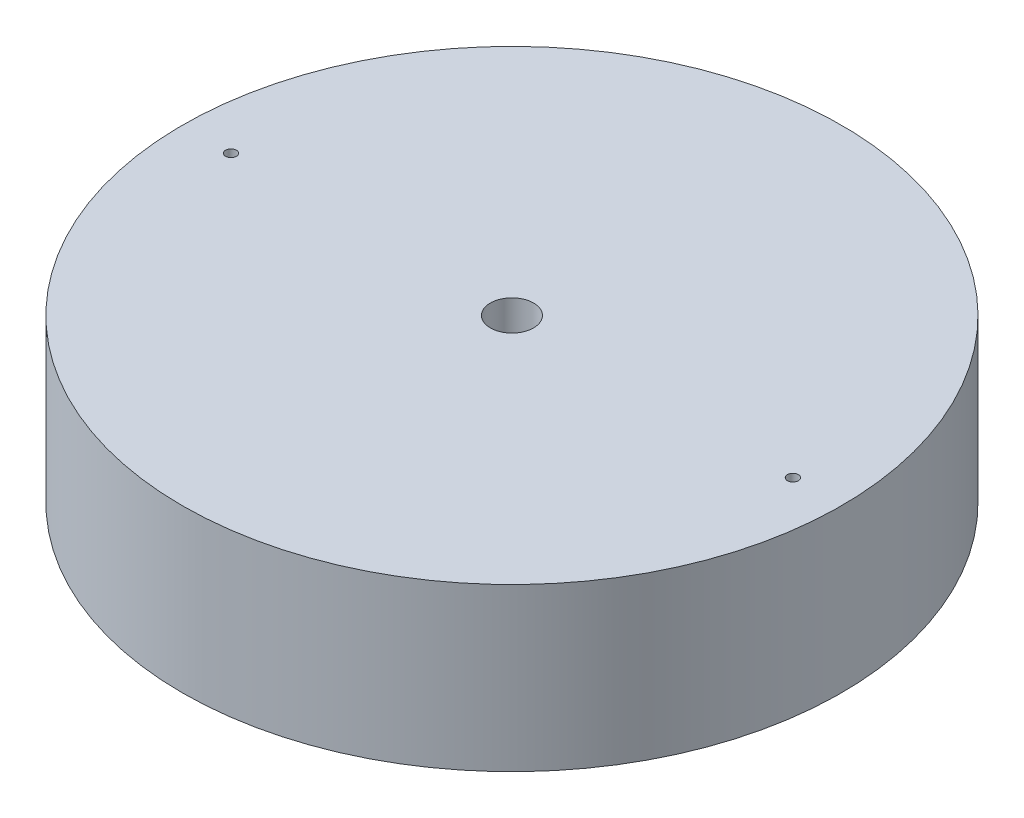
SolidWorks part; units mm, degrees
material "7075-T6 (SN)"
ref_plane "Front Plane" through (0, 0, 0) normal (0, 0, 1) x (1, 0, 0)
ref_plane "Top Plane" through (0, 0, 0) normal (0, 1, 0) x (1, 0, 0)
ref_plane "Right Plane" through (0, 0, 0) normal (1, 0, 0) x (0, 0, -1)
sketch "Sketch1" plane through (0, 0, 0) normal (0, 1, 0) x (1, 0, 0)
  circle A0 centre (0, 0) radius 32.5
extrude "Boss-Extrude1" add sketch "Sketch1" along normal blind 15
sketch "Sketch2" plane through (0, 15, 0) normal (0, 1, 0) x (1, 0, 0)
  circle A0 centre (0, 0) radius 30.5
  circle A1 centre (0, 0) radius 32.5
extrude "Cut-Extrude2" cut sketch "Sketch2" against normal blind 30
sketch "Sketch3" plane through (0, 0, 0) normal (0, -1, 0) x (1, 0, 0)
  circle A0 centre (0, 0) radius 24
  circle A1 centre (0, 0) radius 28
  dimension "D1" = 4
extrude "Cut-Extrude3" cut sketch "Sketch3" against normal blind 7
sketch "Sketch5" plane through (0, 15, 0) normal (0, 1, 0) x (1, 0, 0)
  circle A0 centre (0, 0) radius 26 construction
  circle A1 centre (-26, 0) radius 0.5
  circle A2 centre (26, 0) radius 0.5
extrude "Cut-Extrude5" cut sketch "Sketch5" against normal through all
sketch "Sketch6" plane through (0, 15, 0) normal (0, 1, 0) x (1, 0, 0)
  circle A0 centre (0, 0) radius 2
extrude "Cut-Extrude6" cut sketch "Sketch6" against normal through all
